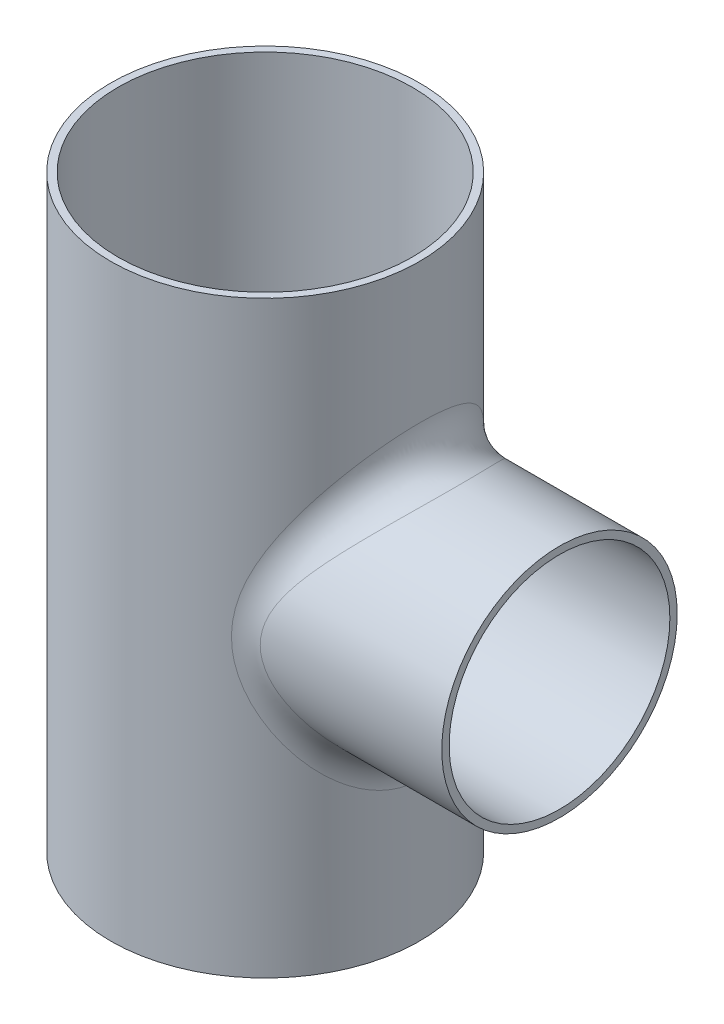
SolidWorks part; units mm, degrees
material "AISI 316 Stainless Steel Sheet (SS)"
ref_plane "Front Plane" through (0, 0, 0) normal (0, 0, 1) x (1, 0, 0)
ref_plane "Top Plane" through (0, 0, 0) normal (0, 1, 0) x (1, 0, 0)
ref_plane "Right Plane" through (0, 0, 0) normal (1, 0, 0) x (0, 0, -1)
sketch "Sketch1" plane through (0, 0, 0) normal (0, 1, 0) x (1, 0, 0)
  circle A0 centre (0, 0) radius 53.34
  dimension "D1" = 106.68
extrude "Boss-Extrude1" add sketch "Sketch1" along normal blind 203.2
sketch "Sketch2" plane through (0, 0, 0) normal (1, 0, 0) x (0, 0, -1)
  circle A0 centre (0, 101.6) radius 40.64
  dimension "D1" = 81.28
extrude "Boss-Extrude2" add sketch "Sketch2" along normal blind 101.6
sketch "Sketch3" plane through (101.6, 0, 0) normal (1, 0, 0) x (0, 0, -1)
  circle A0 centre (0, 101.6) radius 38.1
  dimension "D1" = 76.2
extrude "Cut-Extrude1" cut sketch "Sketch3" against normal blind 101.6
sketch "Sketch4" plane through (0, 203.2, 0) normal (0, 1, 0) x (1, 0, 0)
  circle A0 centre (0, 0) radius 50.8
  dimension "D1" = 101.6
extrude "Cut-Extrude2" cut sketch "Sketch4" against normal through all
fillet "Fillet1" radius 12.7 1 edges at (34.5482, 101.7865, -40.6396)
